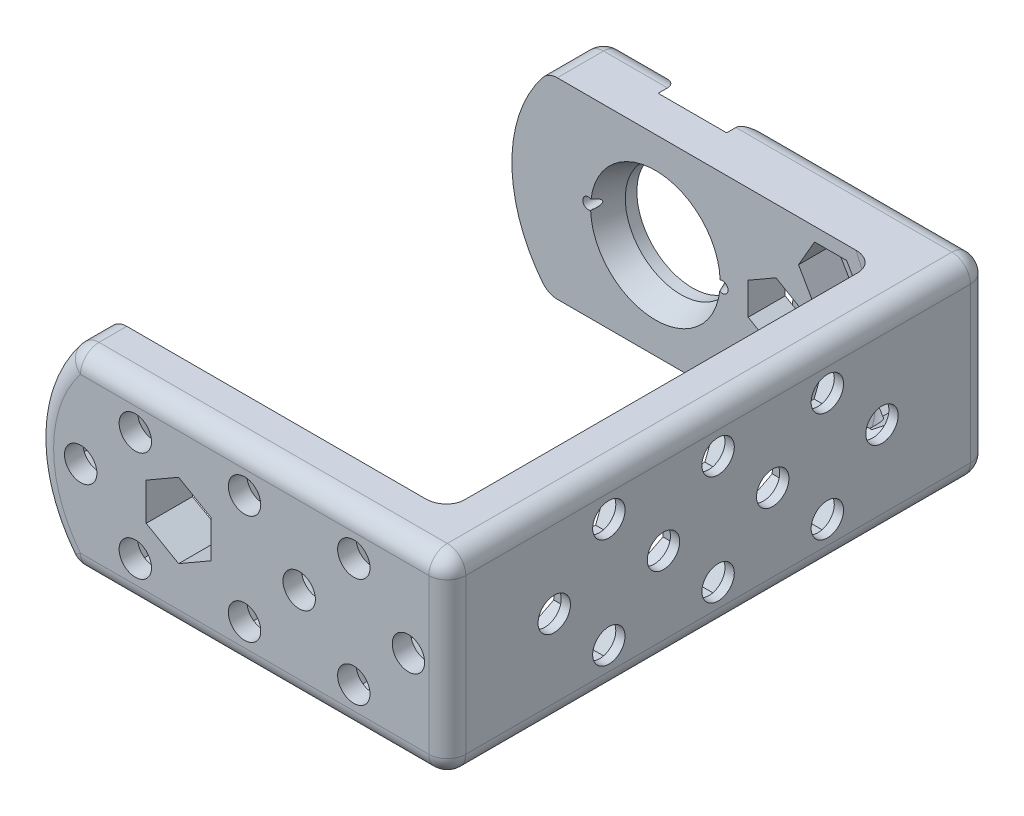
SolidWorks part; units mm, degrees
note: The reader was unsure of these and kept them because the rebuilt part matched: shared geometry of "Эскиз1<5>", "Эскиз1<7>", "Эскиз4<5>", "Эскиз5<4>", "Эскиз6<4>", "Эскиз4<7>", "Эскиз1<9>".
ref_plane "Спереди" through (0, 0, 0) normal (0, 0, 1) x (1, 0, 0)
ref_plane "Сверху" through (0, 0, 0) normal (0, 1, 0) x (1, 0, 0)
ref_plane "Справа" through (0, 0, 0) normal (1, 0, 0) x (0, 0, -1)
sketch "Эскиз1" plane through (0, 0, 0) normal (0, 0, 1) x (1, 0, 0)
  line L0 (29.0242, 0) -> (-15.5, 0) construction
  line L4 (-10.5994, -10.3608) -> (27.0242, -10.3608)
  line L5 (-10.5994, 10.3608) -> (27.0242, 10.3608)
  line L6 (29.0242, -8.3608) -> (29.0242, 8.3608)
  circle A0 centre (0, 0) radius 11
  circle A1 centre (0, 0) radius 6
  arc A2 (-12.1696, -9.5995) -> (-12.1696, 9.5995) centre (0, 0) cw
  circle A3 centre (0, 0) radius 26.0242 construction
  arc A6 (23.8728, -10.3608) -> (23.8728, 10.3608) centre (0, 0) ccw
  arc A7 (-10.5994, 10.3608) -> (-12.1696, 9.5995) centre (-10.5994, 8.3608) ccw
  arc A8 (-10.5994, -10.3608) -> (-12.1696, -9.5995) centre (-10.5994, -8.3608) cw
  arc A9 (27.0242, 10.3608) -> (29.0242, 8.3608) centre (27.0242, 8.3608) cw
  arc A10 (29.0242, -8.3608) -> (27.0242, -10.3608) centre (27.0242, -8.3608) cw
  point P20 (-11.5284, 10.3608)
  point P23 (-11.5284, -10.3608)
  dimension "D1" = 22
  dimension "D2" = 12
  dimension "D3" = 15.5
  dimension "D4" = 26.0242
  dimension "D5" = 3
  dimension "D6" = 2
  dimension "D7" = 20.7216
extrude "Бобышка-Вытянуть1" add sketch "Эскиз1" along normal blind 5 contours L5 A9 L6 A10 L4 A8 A2 A7 | A1
extrude "Бобышка-Вытянуть4" add sketch "Эскиз1<5>" against normal up to surface (2 mm away) contours A8 L4 A0 L5 A7 A2 | L4 A6 L5 A0 | A10 L6 A9 L5 A6 L4
sketch "Эскиз1<5>" plane through (0, 0, 0) normal (0, 0, 1) x (1, 0, 0) same geometry as "Эскиз1"
extrude "Бобышка-Вытянуть5" add sketch "Эскиз1<7>" along normal blind 46.5 from surface at 5 contours A10 L6 A9 L5 A6 L4 starting at face at (7.9852, 0, 5)
sketch "Эскиз1<7>" plane through (0, 0, 0) normal (0, 0, 1) x (1, 0, 0) same geometry as "Эскиз1"
sketch "Эскиз2" plane through (0, 0, 51.5) normal (0, 0, 1) x (1, 0, 0)
  line L0 (-10.5994, -10.3608) -> (27.0242, -10.3608) construction
  line L1 (-10.5994, 10.3608) -> (27.0242, 10.3608) construction
  line L2 (29.0242, -8.3608) -> (29.0242, 8.3608) construction
  line L3 (-10.5994, -10.3608) -> (27.0242, -10.3608)
  line L4 (-10.5994, 10.3608) -> (27.0242, 10.3608)
  line L5 (29.0242, -8.3608) -> (29.0242, 8.3608)
  line L6 (0, -4.0415) -> (0, 4.0415) construction
  line L7 (-3.5, -2.0207) -> (0, -4.0415)
  line L8 (0, -4.0415) -> (3.5, -2.0207)
  line L9 (3.5, -2.0207) -> (3.5, 2.0207)
  line L10 (3.5, 2.0207) -> (0, 4.0415)
  line L11 (0, 4.0415) -> (-3.5, 2.0207)
  line L12 (-3.5, 2.0207) -> (-3.5, -2.0207)
  arc A0 (-12.1696, -9.5995) -> (-10.5994, -10.3608) centre (-10.5994, -8.3608) ccw construction
  arc A1 (-12.1696, 9.5995) -> (-12.1696, -9.5995) centre (0, 0) ccw construction
  arc A2 (-10.5994, 10.3608) -> (-12.1696, 9.5995) centre (-10.5994, 8.3608) ccw construction
  arc A3 (29.0242, 8.3608) -> (27.0242, 10.3608) centre (27.0242, 8.3608) ccw construction
  arc A4 (27.0242, -10.3608) -> (29.0242, -8.3608) centre (27.0242, -8.3608) ccw construction
  arc A5 (-12.1696, -9.5995) -> (-10.5994, -10.3608) centre (-10.5994, -8.3608) ccw
  arc A6 (-12.1696, 9.5995) -> (-12.1696, -9.5995) centre (0, 0) ccw
  arc A7 (-10.5994, 10.3608) -> (-12.1696, 9.5995) centre (-10.5994, 8.3608) ccw
  arc A8 (29.0242, 8.3608) -> (27.0242, 10.3608) centre (27.0242, 8.3608) ccw
  arc A9 (27.0242, -10.3608) -> (29.0242, -8.3608) centre (27.0242, -8.3608) ccw
  circle A10 centre (0, 0) radius 3.5 construction
  circle A11 centre (0, 0) radius 6 construction
  circle A13 centre (0, 0) radius 6 construction
  dimension "D1" = 7
extrude "Бобышка-Вытянуть7" add sketch "Эскиз2" along normal blind 5
fillet "Скругление1" radius 2 20 edges at (-7.1472, -10.3608, -2) (-11.4719, -10.1604, -2) (-7.1472, 10.3608, -2) (-11.4719, 10.1604, -2) (15.3596, 10.3608, -2) (28.4384, 9.775, -2) (29.0242, 0, -2) (15.3596, -10.3608, -2) (-11.4719, -10.1604, 56.5) (-15.5, 0, 56.5) (-11.4719, 10.1604, 56.5) (-15.5, 0, -2) (28.4384, -9.775, -2) (8.2124, -10.3608, 56.5) (28.4384, -9.775, 56.5) (29.0242, 0, 56.5) (28.4384, 9.775, 56.5) (8.2124, 10.3608, 56.5)
sketch "Эскиз3" plane through (0, 0, 0) normal (0, 0, -1) x (-1, 0, 0)
  circle A0 centre (-7.1003, -3.7945) radius 0.6 construction
  circle A1 centre (-7.2439, -0.2975) radius 0.6 construction
  circle A2 centre (-7.3875, 3.1996) radius 0.6 construction
  circle A3 centre (-3.7945, 7.1003) radius 0.6 construction
  circle A4 centre (-0.2975, 7.2439) radius 0.6 construction
  circle A5 centre (3.1996, 7.3875) radius 0.6 construction
  circle A6 centre (7.1003, 3.7945) radius 0.6 construction
  circle A7 centre (7.2439, 0.2975) radius 0.6 construction
  circle A8 centre (7.3875, -3.1996) radius 0.6 construction
  circle A9 centre (3.7945, -7.1003) radius 0.6 construction
  circle A10 centre (0.2975, -7.2439) radius 0.6 construction
  circle A11 centre (-3.1996, -7.3875) radius 0.6 construction
  circle A12 centre (-7.1003, -3.7945) radius 0.6
  circle A13 centre (-7.2439, -0.2975) radius 0.6
  circle A14 centre (-7.3875, 3.1996) radius 0.6
  circle A15 centre (-3.7945, 7.1003) radius 0.6
  circle A16 centre (-0.2975, 7.2439) radius 0.6
  circle A17 centre (3.1996, 7.3875) radius 0.6
  circle A18 centre (7.1003, 3.7945) radius 0.6
  circle A19 centre (7.2439, 0.2975) radius 0.6
  circle A20 centre (7.3875, -3.1996) radius 0.6
  circle A21 centre (3.7945, -7.1003) radius 0.6
  circle A22 centre (0.2975, -7.2439) radius 0.6
  circle A23 centre (-3.1996, -7.3875) radius 0.6
extrude "Вырез-Вытянуть1" cut sketch "Эскиз3" against normal up to surface (5 mm away) contours A13 | A19 up to face at (6, 0, 5)
sketch "Эскиз4" plane through (29.0242, 0, 0) normal (1, 0, 0) x (0, 0, -1)
  line L0 (0, 0) -> (-54.5, 0) construction
  line L1 (0, -8.3608) -> (0, 8.3608) construction
  line L3 (-27.25, 0) -> (-27.25, -8.3608) construction
  line L4 (-30.1492, -1.7321) -> (-30.1492, 1.7321)
  line L5 (-54.5, -8.3608) -> (0, -8.3608) construction
  line L6 (-25.5179, -2.8992) -> (-28.9821, -2.8992)
  line L7 (-28.9821, -2.8992) -> (-30.7141, -5.8992)
  line L8 (-30.7141, -5.8992) -> (-28.9821, -8.8992)
  line L9 (-28.9821, -8.8992) -> (-25.5179, -8.8992)
  line L10 (-25.5179, -8.8992) -> (-23.7859, -5.8992)
  line L11 (-23.7859, -5.8992) -> (-25.5179, -2.8992)
  line L12 (-30.1492, 1.7321) -> (-33.1492, 3.4641)
  line L13 (-33.1492, 3.4641) -> (-36.1492, 1.7321)
  line L14 (-36.1492, 1.7321) -> (-36.1492, -1.7321)
  line L15 (-36.1492, -1.7321) -> (-33.1492, -3.4641)
  line L16 (-33.1492, -3.4641) -> (-30.1492, -1.7321)
  line L17 (-27.25, 0) -> (-35.6108, 0) construction
  line L18 (-28.9821, 2.8992) -> (-25.5179, 2.8992)
  line L19 (-25.5179, 2.8992) -> (-23.7859, 5.8992)
  line L20 (-23.7859, 5.8992) -> (-25.5179, 8.8992)
  line L21 (-25.5179, 8.8992) -> (-28.9821, 8.8992)
  line L22 (-28.9821, 8.8992) -> (-30.7141, 5.8992)
  line L23 (-30.7141, 5.8992) -> (-28.9821, 2.8992)
  line L24 (-27.25, 0) -> (-27.25, 8.3608) construction
  line L25 (-24.3508, 1.7321) -> (-24.3508, -1.7321)
  line L26 (-24.3508, -1.7321) -> (-21.3508, -3.4641)
  line L27 (-21.3508, -3.4641) -> (-18.3508, -1.7321)
  line L28 (-18.3508, -1.7321) -> (-18.3508, 1.7321)
  line L29 (-18.3508, 1.7321) -> (-21.3508, 3.4641)
  line L30 (-21.3508, 3.4641) -> (-24.3508, 1.7321)
  line L31 (-27.25, 0) -> (-18.8892, 0) construction
  line L32 (-13.7179, -2.8992) -> (-17.1821, -2.8992)
  line L33 (-54.5, 10.3608) -> (0, 10.3608) construction
  line L34 (-17.1821, -2.8992) -> (-18.9141, -5.8992)
  line L35 (-18.9141, -5.8992) -> (-17.1821, -8.8992)
  line L36 (-17.1821, -8.8992) -> (-13.7179, -8.8992)
  line L37 (-13.7179, -8.8992) -> (-11.9859, -5.8992)
  line L38 (-11.9859, -5.8992) -> (-13.7179, -2.8992)
  line L39 (-17.1821, 2.8992) -> (-13.7179, 2.8992)
  line L40 (-13.7179, 2.8992) -> (-11.9859, 5.8992)
  line L41 (-11.9859, 5.8992) -> (-13.7179, 8.8992)
  line L42 (-13.7179, 8.8992) -> (-17.1821, 8.8992)
  line L43 (-17.1821, 8.8992) -> (-18.9141, 5.8992)
  line L44 (-18.9141, 5.8992) -> (-17.1821, 2.8992)
  line L45 (-12.5508, 1.7321) -> (-12.5508, -1.7321)
  line L46 (-12.5508, -1.7321) -> (-9.5508, -3.4641)
  line L47 (-9.5508, -3.4641) -> (-6.5508, -1.7321)
  line L48 (-6.5508, -1.7321) -> (-6.5508, 1.7321)
  line L49 (-6.5508, 1.7321) -> (-9.5508, 3.4641)
  line L50 (-9.5508, 3.4641) -> (-12.5508, 1.7321)
  line L51 (-15.45, 0) -> (-15.45, -8.3608) construction
  line L52 (-15.45, 0) -> (-23.8108, 0) construction
  line L53 (-15.45, 0) -> (-15.45, 8.3608) construction
  line L54 (-15.45, 0) -> (-7.0892, 0) construction
  line L55 (-37.3179, -2.8992) -> (-40.7821, -2.8992)
  line L56 (-40.7821, -8.8992) -> (-37.3179, -8.8992)
  line L57 (-37.3179, -8.8992) -> (-35.5859, -5.8992)
  line L58 (-35.5859, -5.8992) -> (-37.3179, -2.8992)
  line L59 (-40.7821, -2.8992) -> (-42.5141, -5.8992)
  line L60 (-42.5141, -5.8992) -> (-40.7821, -8.8992)
  line L61 (-40.7821, 2.8992) -> (-37.3179, 2.8992)
  line L62 (-37.3179, 2.8992) -> (-35.5859, 5.8992)
  line L63 (-35.5859, 5.8992) -> (-37.3179, 8.8992)
  line L64 (-37.3179, 8.8992) -> (-40.7821, 8.8992)
  line L65 (-42.5141, 5.8992) -> (-40.7821, 2.8992)
  line L66 (-40.7821, 8.8992) -> (-42.5141, 5.8992)
  line L67 (-41.9492, -1.7321) -> (-41.9492, 1.7321)
  line L68 (-41.9492, 1.7321) -> (-44.9492, 3.4641)
  line L69 (-44.9492, 3.4641) -> (-47.9492, 1.7321)
  line L70 (-47.9492, 1.7321) -> (-47.9492, -1.7321)
  line L71 (-47.9492, -1.7321) -> (-44.9492, -3.4641)
  line L72 (-44.9492, -3.4641) -> (-41.9492, -1.7321)
  line L73 (-54.5, 8.3608) -> (-54.5, -8.3608) construction
  line L74 (-39.05, 5.8992) -> (-39.05, -5.8992) construction
  circle A0 centre (-27.25, -5.8992) radius 1.75
  circle A1 centre (-27.25, -5.8992) radius 3 construction
  circle A2 centre (-33.1492, 0) radius 1.75
  circle A3 centre (-33.1492, 0) radius 3 construction
  circle A4 centre (-27.25, 5.8992) radius 1.75
  circle A5 centre (-27.25, 5.8992) radius 3 construction
  circle A6 centre (-21.3508, 0) radius 1.75
  circle A7 centre (-21.3508, 0) radius 3 construction
  circle A8 centre (-15.45, -5.8992) radius 1.75
  circle A9 centre (-15.45, 5.8992) radius 1.75
  circle A10 centre (-9.5508, 0) radius 1.75
  circle A11 centre (-15.45, -5.8992) radius 3 construction
  circle A12 centre (-15.45, 5.8992) radius 3 construction
  circle A13 centre (-9.5508, 0) radius 3 construction
  circle A14 centre (-39.05, -5.8992) radius 1.75
  circle A15 centre (-39.05, -5.8992) radius 3 construction
  circle A16 centre (-39.05, 5.8992) radius 1.75
  circle A17 centre (-39.05, 5.8992) radius 3 construction
  circle A18 centre (-44.9492, 0) radius 1.75
  circle A19 centre (-44.9492, 0) radius 3 construction
  point P52 (-27.25, 0)
  point P86 (-15.45, 0)
  line M37 (-54.5, -8.3608) -> (0, -8.3608)
  line M39 (0, 8.3608) -> (-54.5, 8.3608)
  dimension "D1" = 3.5
  dimension "D2" = 6
  dimension "D4" = 5.8992
  dimension "D5" = 1.4616
  dimension "D8" = 11.8
  dimension "D9" = 11.8
  dimension "D10" = 11.8
  dimension "D6" = 2
  dimension "D7" = 2
  dimension "D3" = 4
extrude "Вырез-Вытянуть2" cut sketch "Эскиз4" against normal through all contours A6 | A4 | A2 | A18 | A14 | A16 | A8 | A10 | A9 | A0
extrude "Вырез-Вытянуть4" cut sketch "Эскиз4<5>" along normal offset from surface (5 mm away) 1 from offset 6 contours L59 L60 L57 L58 L55 A14 M37 | L71 L72 L67 L68 L69 L70 A18 | L66 L65 L61 L62 L63 A16 M39 | L15 L16 L4 L12 L13 L14 A2 | L22 L23 L18 L19 L20 A4 M39 | L10 L11 L6 L7 L8 A0 M37 | L29 L30 L25 L26 L27 L28 A6 | L43 L44 L39 L40 L41 A9 M39 | L37 L38 L32 L34 L35 A8 M37 | L9 L10 L8 M37 | L36 L37 L35 M37 | L42 L43 L41 M39 | L21 L22 L20 M39 | L64 L66 L63 M39 | L60 L56 L57 M37 up to face at (29.0242, -5.8992, 25.5) offset against normal yes
sketch "Эскиз4<5>" plane through (29.0242, 0, 0) normal (1, 0, 0) x (0, 0, -1) same geometry as "Эскиз4"
sketch "Эскиз5" plane through (0, 0, 56.5) normal (0, 0, 1) x (1, 0, 0)
  line L0 (27.0242, 0) -> (-23.5928, 0) construction
  line L2 (18.9242, 5.9) -> (18.9242, -5.9) construction
  line L3 (16.0242, -1.7321) -> (16.0242, 1.7321)
  line L4 (20.6562, -2.9) -> (17.1921, -2.9)
  line L5 (17.1921, -2.9) -> (15.4601, -5.9)
  line L6 (15.4601, -5.9) -> (17.1921, -8.9)
  line L7 (17.1921, -8.9) -> (20.6562, -8.9)
  line L8 (20.6562, -8.9) -> (22.3883, -5.9)
  line L9 (22.3883, -5.9) -> (20.6562, -2.9)
  line L10 (16.0242, 1.7321) -> (13.0242, 3.4641)
  line L11 (13.0242, 3.4641) -> (10.0242, 1.7321)
  line L12 (10.0242, 1.7321) -> (10.0242, -1.7321)
  line L13 (10.0242, -1.7321) -> (13.0242, -3.4641)
  line L14 (13.0242, -3.4641) -> (16.0242, -1.7321)
  line L15 (17.1921, 2.9) -> (20.6562, 2.9)
  line L16 (20.6562, 2.9) -> (22.3883, 5.9)
  line L17 (22.3883, 5.9) -> (20.6562, 8.9)
  line L18 (20.6562, 8.9) -> (17.1921, 8.9)
  line L19 (17.1921, 8.9) -> (15.4601, 5.9)
  line L20 (15.4601, 5.9) -> (17.1921, 2.9)
  line L21 (21.8242, 1.7321) -> (21.8242, -1.7321)
  line L22 (21.8242, -1.7321) -> (24.8242, -3.4641)
  line L23 (24.8242, -3.4641) -> (27.8242, -1.7321)
  line L24 (27.8242, -1.7321) -> (27.8242, 1.7321)
  line L25 (27.8242, 1.7321) -> (24.8242, 3.4641)
  line L26 (24.8242, 3.4641) -> (21.8242, 1.7321)
  line L28 (4.2242, -1.7321) -> (4.2242, 1.7321)
  line L29 (8.8562, -2.9) -> (5.3921, -2.9)
  line L30 (5.3921, -2.9) -> (3.6601, -5.9)
  line L31 (3.6601, -5.9) -> (5.3921, -8.9)
  line L32 (5.3921, -8.9) -> (8.8562, -8.9)
  line L33 (8.8562, -8.9) -> (10.5883, -5.9)
  line L34 (10.5883, -5.9) -> (8.8562, -2.9)
  line L35 (4.2242, 1.7321) -> (1.2242, 3.4641)
  line L36 (1.2242, 3.4641) -> (-1.7758, 1.7321)
  line L37 (-1.7758, 1.7321) -> (-1.7758, -1.7321)
  line L38 (-1.7758, -1.7321) -> (1.2242, -3.4641)
  line L39 (1.2242, -3.4641) -> (4.2242, -1.7321)
  line L40 (5.3921, 2.9) -> (8.8562, 2.9)
  line L41 (8.8562, 2.9) -> (10.5883, 5.9)
  line L42 (10.5883, 5.9) -> (8.8562, 8.9)
  line L43 (8.8562, 8.9) -> (5.3921, 8.9)
  line L44 (5.3921, 8.9) -> (3.6601, 5.9)
  line L45 (3.6601, 5.9) -> (5.3921, 2.9)
  line L46 (7.1242, 5.9) -> (7.1242, -5.9) construction
  line L47 (-7.5758, -1.7321) -> (-7.5758, 1.7321)
  line L48 (-2.9438, -2.9) -> (-6.4079, -2.9)
  line L49 (-6.4079, -2.9) -> (-8.1399, -5.9)
  line L50 (-8.1399, -5.9) -> (-6.4079, -8.9)
  line L51 (-6.4079, -8.9) -> (-2.9438, -8.9)
  line L52 (-2.9438, -8.9) -> (-1.2117, -5.9)
  line L53 (-1.2117, -5.9) -> (-2.9438, -2.9)
  line L54 (-7.5758, 1.7321) -> (-10.5758, 3.4641)
  line L55 (-10.5758, 3.4641) -> (-13.5758, 1.7321)
  line L56 (-13.5758, 1.7321) -> (-13.5758, -1.7321)
  line L57 (-13.5758, -1.7321) -> (-10.5758, -3.4641)
  line L58 (-10.5758, -3.4641) -> (-7.5758, -1.7321)
  line L59 (-6.4079, 2.9) -> (-2.9438, 2.9)
  line L60 (-2.9438, 2.9) -> (-1.2117, 5.9)
  line L61 (-1.2117, 5.9) -> (-2.9438, 8.9)
  line L62 (-2.9438, 8.9) -> (-6.4079, 8.9)
  line L63 (-6.4079, 8.9) -> (-8.1399, 5.9)
  line L64 (-8.1399, 5.9) -> (-6.4079, 2.9)
  line L65 (-4.6758, 5.9) -> (-4.6758, -5.9) construction
  line L67 (27.0242, -8.3608) -> (27.0242, 8.3608) construction
  line L68 (29.0242, 8.3608) -> (29.0242, -8.3608) construction
  line L85 (-19.3758, -1.7321) -> (-19.3758, 1.7321) [skipped]
  line L86 (-14.7438, -2.9) -> (-18.2079, -2.9) [skipped]
  line L87 (-18.2079, -2.9) -> (-19.9399, -5.9) [skipped]
  line L88 (-19.9399, -5.9) -> (-18.2079, -8.9) [skipped]
  line L89 (-18.2079, -8.9) -> (-14.7438, -8.9) [skipped]
  line L90 (-14.7438, -8.9) -> (-13.0117, -5.9) [skipped]
  line L91 (-13.0117, -5.9) -> (-14.7438, -2.9) [skipped]
  line L92 (-19.3758, 1.7321) -> (-22.3758, 3.4641) [skipped]
  line L93 (-22.3758, -3.4641) -> (-19.3758, -1.7321) [skipped]
  line L94 (-18.2079, 2.9) -> (-14.7438, 2.9) [skipped]
  line L95 (-14.7438, 8.9) -> (-18.2079, 8.9) [skipped]
  line L96 (-18.2079, 8.9) -> (-19.9399, 5.9) [skipped]
  line L97 (-19.9399, 5.9) -> (-18.2079, 2.9) [skipped]
  line L98 (-16.4758, 5.9) -> (-16.4758, -5.9) construction
  line L99 (-22.3758, 3.4641) -> (-25.3758, 1.7321) [skipped]
  line L100 (-25.3758, 1.7321) -> (-25.3758, -1.7321) [skipped]
  line L101 (-25.3758, -1.7321) -> (-22.3758, -3.4641) [skipped]
  line L102 (-14.7438, 2.9) -> (-13.0117, 5.9) [skipped]
  line L103 (-13.0117, 5.9) -> (-14.7438, 8.9) [skipped]
  circle A1 centre (18.9242, -5.9) radius 1.75
  circle A2 centre (18.9242, -5.9) radius 3 construction
  circle A3 centre (13.0242, 0) radius 1.75
  circle A4 centre (13.0242, 0) radius 3 construction
  circle A5 centre (18.9242, 5.9) radius 1.75
  circle A6 centre (18.9242, 5.9) radius 3 construction
  circle A7 centre (24.8242, 0) radius 1.75
  circle A8 centre (24.8242, 0) radius 3 construction
  circle A9 centre (7.1242, -5.9) radius 1.75
  circle A10 centre (1.2242, 0) radius 1.75
  circle A11 centre (7.1242, 5.9) radius 1.75
  circle A12 centre (7.1242, -5.9) radius 3 construction
  circle A13 centre (1.2242, 0) radius 3 construction
  circle A14 centre (7.1242, 5.9) radius 3 construction
  circle A15 centre (-4.6758, -5.9) radius 1.75
  circle A16 centre (-10.5758, 0) radius 1.75
  circle A17 centre (-4.6758, 5.9) radius 1.75
  circle A18 centre (-4.6758, -5.9) radius 3 construction
  circle A19 centre (-10.5758, 0) radius 3 construction
  circle A20 centre (-4.6758, 5.9) radius 3 construction
  circle A27 centre (-16.4758, -5.9) radius 1.75 [skipped]
  circle A28 centre (-16.4758, 5.9) radius 1.75 [skipped]
  circle A29 centre (-16.4758, -5.9) radius 3 construction
  circle A30 centre (-22.3758, 0) radius 1.75 [skipped]
  circle A31 centre (-22.3758, 0) radius 3 construction
  circle A32 centre (-16.4758, 5.9) radius 3 construction
  point P1 (-16.4758, 0)
  point P47 (18.9242, 0)
  point P75 (7.1242, 0)
  point P103 (-4.6758, 0)
  dimension "D1" = 3.5
  dimension "D2" = 6
  dimension "D3" = 5.9
  dimension "D5" = 1.2
  dimension "D7" = 11.8
  dimension "D6" = 4
  dimension "D4" = 4
extrude "Вырез-Вытянуть5" cut sketch "Эскиз5" against normal up to surface (5 mm away) contours A16 | A15 | A9 | A11 | A3 | A5 | A1 | A17 | A7 up to face at (-5.9364, 0, 51.5)
ref_plane "Плоскость1" through (0, 0, 51.5) normal (0, 0, -1) x (-1, 0, 0)
extrude "Вырез-Вытянуть6" cut sketch "Эскиз5<4>" along normal blind 3 and the other way blind 3 from surface at -5
sketch "Эскиз5<4>" plane through (0, 0, 56.5) normal (0, 0, 1) x (1, 0, 0) same geometry as "Эскиз5"
sketch "Эскиз6" plane through (0, 0, -2) normal (0, 0, -1) x (-1, 0, 0)
  line L0 (-10.0242, 1.7321) -> (-13.0242, 3.4641) construction
  line L1 (-13.0242, 3.4641) -> (-16.0242, 1.7321) construction
  line L2 (-16.0242, 1.7321) -> (-16.0242, -1.7321) construction
  line L3 (-16.0242, -1.7321) -> (-13.0242, -3.4641) construction
  line L4 (-13.0242, -3.4641) -> (-10.0242, -1.7321) construction
  line L5 (-10.0242, -1.7321) -> (-10.0242, 1.7321) construction
  line L6 (-17.1921, 8.9) -> (-20.6562, 8.9) construction
  line L7 (-20.6562, 8.9) -> (-22.3883, 5.9) construction
  line L8 (-22.3883, 5.9) -> (-20.6562, 2.9) construction
  line L9 (-20.6562, 2.9) -> (-17.1921, 2.9) construction
  line L10 (-17.1921, 2.9) -> (-15.4601, 5.9) construction
  line L11 (-15.4601, 5.9) -> (-17.1921, 8.9) construction
  line L12 (-24.8242, -3.4641) -> (-21.8242, -1.7321) construction
  line L13 (-21.8242, -1.7321) -> (-21.8242, 1.7321) construction
  line L14 (-21.8242, 1.7321) -> (-24.8242, 3.4641) construction
  line L15 (-24.8242, 3.4641) -> (-27.8242, 1.7321) construction
  line L16 (-27.8242, 1.7321) -> (-27.8242, -1.7321) construction
  line L17 (-27.8242, -1.7321) -> (-24.8242, -3.4641) construction
  line L18 (-15.4601, -5.9) -> (-17.1921, -2.9) construction
  line L19 (-17.1921, -2.9) -> (-20.6562, -2.9) construction
  line L20 (-20.6562, -2.9) -> (-22.3883, -5.9) construction
  line L21 (-22.3883, -5.9) -> (-20.9675, -8.3608) construction
  line L23 (-16.8808, -8.3608) -> (-15.4601, -5.9) construction
  line L24 (-10.0242, 1.7321) -> (-13.0242, 3.4641)
  line L25 (-13.0242, 3.4641) -> (-16.0242, 1.7321)
  line L26 (-16.0242, 1.7321) -> (-16.0242, -1.7321)
  line L27 (-16.0242, -1.7321) -> (-13.0242, -3.4641)
  line L28 (-13.0242, -3.4641) -> (-10.0242, -1.7321)
  line L29 (-10.0242, -1.7321) -> (-10.0242, 1.7321)
  line L30 (-17.1921, 8.9) -> (-20.6562, 8.9)
  line L31 (-20.6562, 8.9) -> (-22.3883, 5.9)
  line L32 (-22.3883, 5.9) -> (-20.6562, 2.9)
  line L33 (-20.6562, 2.9) -> (-17.1921, 2.9)
  line L34 (-17.1921, 2.9) -> (-15.4601, 5.9)
  line L35 (-15.4601, 5.9) -> (-17.1921, 8.9)
  line L36 (-24.8242, -3.4641) -> (-21.8242, -1.7321)
  line L37 (-21.8242, -1.7321) -> (-21.8242, 1.7321)
  line L38 (-21.8242, 1.7321) -> (-24.8242, 3.4641)
  line L39 (-24.8242, 3.4641) -> (-27.8242, 1.7321)
  line L40 (-27.8242, 1.7321) -> (-27.8242, -1.7321)
  line L41 (-27.8242, -1.7321) -> (-24.8242, -3.4641)
  line L42 (-15.4601, -5.9) -> (-17.1921, -2.9)
  line L43 (-17.1921, -2.9) -> (-20.6562, -2.9)
  line L44 (-20.6562, -2.9) -> (-22.3883, -5.9)
  line L45 (-22.3883, -5.9) -> (-20.9675, -8.3608)
  line L46 (-20.9675, -8.3608) -> (-16.8808, -8.3608)
  line L47 (-16.8808, -8.3608) -> (-15.4601, -5.9)
  circle A0 centre (-18.9242, 5.9) radius 1.75 construction
  circle A1 centre (-13.0242, 0) radius 1.75 construction
  circle A2 centre (-18.9242, -5.9) radius 1.75 construction
  circle A3 centre (-24.8242, 0) radius 1.75 construction
  circle A4 centre (-18.9242, 5.9) radius 1.75
  circle A5 centre (-13.0242, 0) radius 1.75
  circle A6 centre (-18.9242, -5.9) radius 1.75
  circle A7 centre (-24.8242, 0) radius 1.75
extrude "Вырез-Вытянуть7" cut sketch "Эскиз6" against normal up to surface (7 mm away) contours A6 | A5 | A4 | A7 up to face at (-6.6439, 0.2975, 5)
ref_plane "Плоскость2" through (0, 0, 5) normal (0, 0, 1) x (1, 0, 0)
extrude "Вырез-Вытянуть8" cut sketch "Эскиз6<4>" along normal blind 4 and the other way blind 3 from surface at -7 contours L33 L34 L35 L30 L31 L32 | L37 L38 L39 L40 L41 L36 | L26 L27 L28 L29 L24 L25 | L42 L43 L44 L45 L46 L47 starting at plane "Плоскость2"
sketch "Эскиз6<4>" plane through (0, 0, -2) normal (0, 0, -1) x (-1, 0, 0) same geometry as "Эскиз6"
extrude "Вырез-Вытянуть9" cut sketch "Эскиз4<7>" along normal offset from surface (3 mm away) 1 from offset 4 contours L49 L50 L45 L46 L47 L48 A10 up to face at (29.0242, -5.8992, 25.5) offset against normal yes
sketch "Эскиз4<7>" plane through (29.0242, 0, 0) normal (1, 0, 0) x (0, 0, -1) same geometry as "Эскиз4"
sketch "Эскиз7" plane through (0, 0, 5) normal (0, 0, 1) x (1, 0, 0)
  circle A0 centre (0, 0) radius 7
  dimension "D1" = 14
extrude "Вырез-Вытянуть10" cut sketch "Эскиз7" against normal blind 3 draft 20
extrude "Вырез-Вытянуть11" cut sketch "Эскиз1<9>" along normal blind 1 contours L5 A0 L4 A1
sketch "Эскиз1<9>" plane through (0, 0, 0) normal (0, 0, 1) x (1, 0, 0) same geometry as "Эскиз1"
